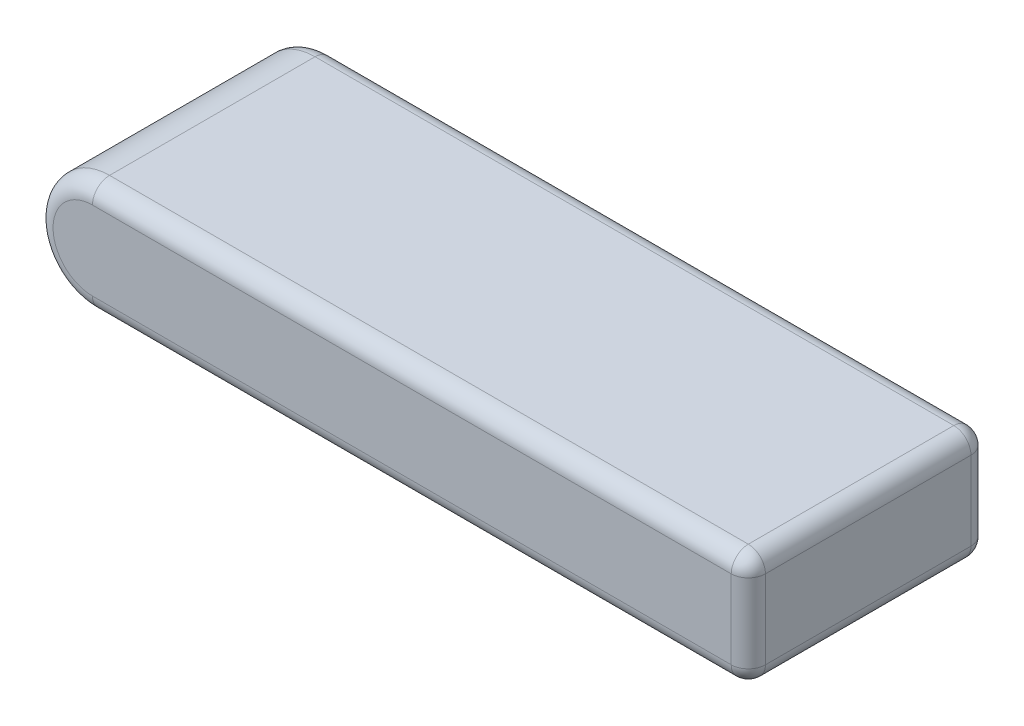
SolidWorks part; units mm, degrees
ref_plane "Front Plane" through (0, 0, 0) normal (0, 0, 1) x (1, 0, 0)
ref_plane "Top Plane" through (0, 0, 0) normal (0, 1, 0) x (1, 0, 0)
ref_plane "Right Plane" through (0, 0, 0) normal (1, 0, 0) x (0, 0, -1)
sketch "Sketch1" plane through (0, 0, 0) normal (0, 1, 0) x (1, 0, 0)
  line L1 (-52, -17.5) -> (52, -17.5)
  line L2 (-52, -17.5) -> (-52, 17.5)
  line L3 (-52, 17.5) -> (52, 17.5)
  line L4 (52, -17.5) -> (52, 17.5)
  line L5 (0, 17.5) -> (0, -17.5) construction
  line L6 (-52, 0) -> (52, 0) construction
  point P4 (0, 0)
  point P72 (0, 0)
  dimension "D1" = 35
  dimension "D2" = 104
extrude "Boss-Extrude1" add sketch "Sketch1" along normal blind 16.5
fillet "Fillet2" 2 edges at (-52, 16.5, 0) (-52, 0, 0) type full round first side face at (0, 16.5, 0) second side face at (0, 0, 0) middle face at (-52, 8.25, 0)
fillet "Fillet3" radius 2.5 10 edges at (-52, 8.25, -17.5) (4.125, 0, -17.5) (4.125, 16.5, -17.5) (52, 16.5, 0) (52, 8.25, -17.5) (52, 0, 0) (52, 8.25, 17.5) (4.125, 0, 17.5) (-52, 8.25, 17.5) (4.125, 16.5, 17.5)
